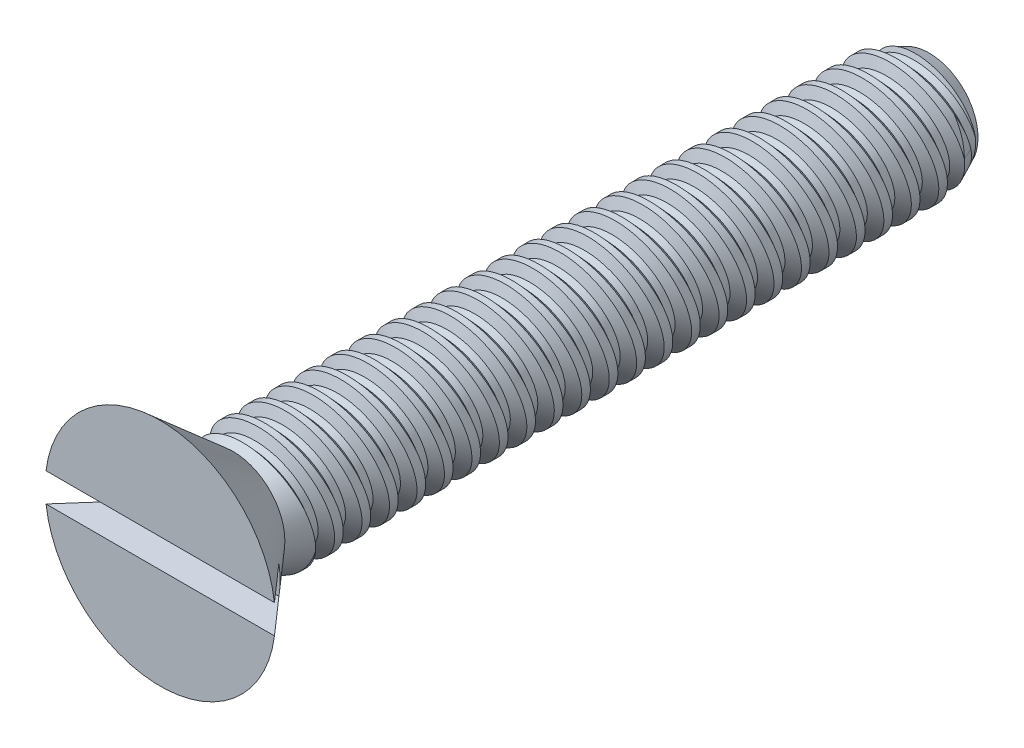
SolidWorks part; units mm, degrees
ref_plane "Front" through (0, 0, 0) normal (0, 0, 1) x (1, 0, 0)
ref_plane "Top" through (0, 0, 0) normal (0, 1, 0) x (1, 0, 0)
ref_plane "Right" through (0, 0, 0) normal (1, 0, 0) x (0, 0, -1)
sketch "Sketch1" plane through (0, 0, 0) normal (0, 0, 1) x (1, 0, 0)
  circle A0 centre (0, 0) radius 3.3274
  dimension "Head Dia" = 6.6548
extrude "Extrude3" add sketch "Sketch1" along normal blind 2.1082
sketch "Sketch11" plane through (0, 0, 0) normal (1, 0, 0) x (0, 0, -1)
  line L0 (0.4414, 0) -> (-2.8754, 0) construction
  line L2 (0, 1.4948) -> (-2.1082, 3.3274)
  line L3 (0, -3.3274) -> (0, 3.3274) construction
  line L5 (-2.1082, 3.3274) -> (0, 3.3274)
  line L7 (0, 3.3274) -> (0, 1.4948)
  line L8 (0, 3.3274) -> (-2.1082, 3.3274) construction
  line L10 (-2.1082, 3.3274) -> (-2.1082, -3.3274) construction
  line L11 (0, -1.4948) -> (-2.1082, -3.3274) construction
  dimension "D1" = 82
revolve "Cut-Revolve3" cut sketch "Sketch11" angle 360 about L0
sketch "Sketch4" plane through (0, 0, 0) normal (1, 0, 0) x (0, 0, -1)
  line L0 (0, 0) -> (20.1168, 0)
  line L2 (20.1168, -1.7526) -> (0, -1.7526) construction
  line L3 (20.1168, 0) -> (20.1168, 1.7526)
  line L4 (20.1168, 1.7526) -> (0, 1.7526)
  line L5 (-2.1082, 3.3274) -> (-2.1082, -3.3274) construction
  line L6 (0, 1.7526) -> (0, 0)
  line L7 (20.1168, 0) -> (22.6568, 0) construction
  dimension "D1" = 2.54
  dimension "Screw Dia" = 3.5052
  dimension "Screw Length" = 22.225
  dimension "Body Length" = 20.1168
revolve "Revolve1" add sketch "Sketch4" angle 360 about L7
sketch "Sketch5" plane through (0, 0, 0) normal (1, 0, 0) x (0, 0, -1)
  line L0 (0, 1.7526) -> (0.0968, 1.7745) construction
  line L1 (0, 1.7526) -> (0, -1.7526) construction
  line L2 (0.0968, 1.7745) -> (0.4336, 1.4103)
  line L3 (0.4336, 1.4103) -> (0.6271, 1.4541)
  line L4 (0.6271, 1.4541) -> (0.7741, 1.9279)
  line L5 (0.7741, 1.9279) -> (0.0968, 1.7745)
  line L6 (0.5303, 1.4322) -> (0.4355, 1.8512) construction
  line L7 (0, 1.7526) -> (0, 0) construction
  line L8 (0, -1.7526) -> (0.7938, -1.7526) construction
  line L11 (0.7938, -1.7526) -> (0, 1.7526) construction
  line L12 (20.1168, 1.7526) -> (0, 1.7526) construction
  line L13 (20.1168, -1.7526) -> (0, -1.7526) construction
  line L14 (0.4578, 1.7526) -> (1.2515, -1.7526) construction
  line L15 (0, -0.1935) -> (1.7093, 0.1935) construction
  point P22 (0.8547, 0)
  dimension "D1" = 0.7937
  dimension "Pitch" = 0.7937
  dimension "D2" = 0.0992
  dimension "D3" = 0.1984
  dimension "D4" = 60
revolve "Cut-Revolve1" cut sketch "Sketch5" angle 360 about L15
sketch "Sketch13" plane through (0, 0, 0) normal (1, 0, 0) x (0, 0, -1)
  line L0 (20.1168, 1.4103) -> (19.3827, 1.7526)
  line L1 (20.1168, 0) -> (20.1168, 1.7526) construction
  line L2 (19.3827, 1.7526) -> (20.1168, 1.7526)
  line L3 (20.1168, 1.7526) -> (20.1168, 1.4103)
  line L4 (20.1168, 1.7526) -> (0, 1.7526) construction
  line L5 (0, 0) -> (19.3827, 0) construction
  line L6 (0, 0) -> (20.1168, 0) construction
  line L7 (19.3827, 1.7526) -> (19.3827, -1.7526) construction
  dimension "D1" = 25
  dimension "D2" = 3.5052
revolve "Cut-Revolve4" cut sketch "Sketch13" angle 360 about L5
sketch "Sketch16" plane through (0, 0, 0) normal (1, 0, 0) x (0, 0, -1)
  line L0 (0, 1.4948) -> (0.7084, 1.7526)
  line L1 (0.7084, 1.7526) -> (0, 1.7526)
  line L2 (0, 1.7526) -> (0, 1.4948)
  line L3 (0, 1.7526) -> (0, 0) construction
  line L4 (20.1168, 1.7526) -> (0, 1.7526) construction
  line L5 (0, 1.4948) -> (-2.1082, 3.3274) construction
  line L6 (0, 1.4948) -> (-2.1082, 3.3274) construction
  line L7 (0, 0) -> (20.1168, 0) construction
  line L8 (0, 0) -> (20.1168, 0) construction
  dimension "D1" = 20
revolve "Cut-Revolve5" cut sketch "Sketch16" angle 360 about L8
pattern_linear "LPattern2" count 25 spacing 0.7937 along (0, 0, -1)
sketch "Sketch15" plane through (0, 0, 2.1082) normal (0, 0, 1) x (1, 0, 0)
  line L0 (-3.3274, 0.4159) -> (3.3274, -0.4159) construction
  line L1 (-3.3274, 0.4159) -> (3.3274, 0.4159)
  line L2 (-3.3274, 0.4159) -> (-3.3274, -0.4159)
  line L3 (-3.3274, -0.4159) -> (3.3274, -0.4159)
  line L4 (3.3274, 0.4159) -> (3.3274, -0.4159)
  circle A0 centre (0, 0) radius 3.3274 construction
  dimension "Slot Width" = 0.8318
extrude "Cut-Extrude5" cut sketch "Sketch15" against normal blind 1.0541
equation "\"D2@Sketch5\"=\"Pitch@Sketch5\"/8"
equation "\"D3@Sketch5\"=\"Pitch@Sketch5\"/4"
equation "\"D3@LPattern2\"=\"Pitch@Sketch5\""
equation "\"D1@LPattern2\"=\"Body Length@Sketch4\"/\"Pitch@Sketch5\""
equation "\"D1@Sketch5\"=\"Pitch@Sketch5\""
equation "\"Slot Width@Sketch15\"=\"Head Dia@Sketch1\"/8"
equation "\"Slot Depth@Cut-Extrude5\"=\"Head Ht@Extrude3\"/ 2"
